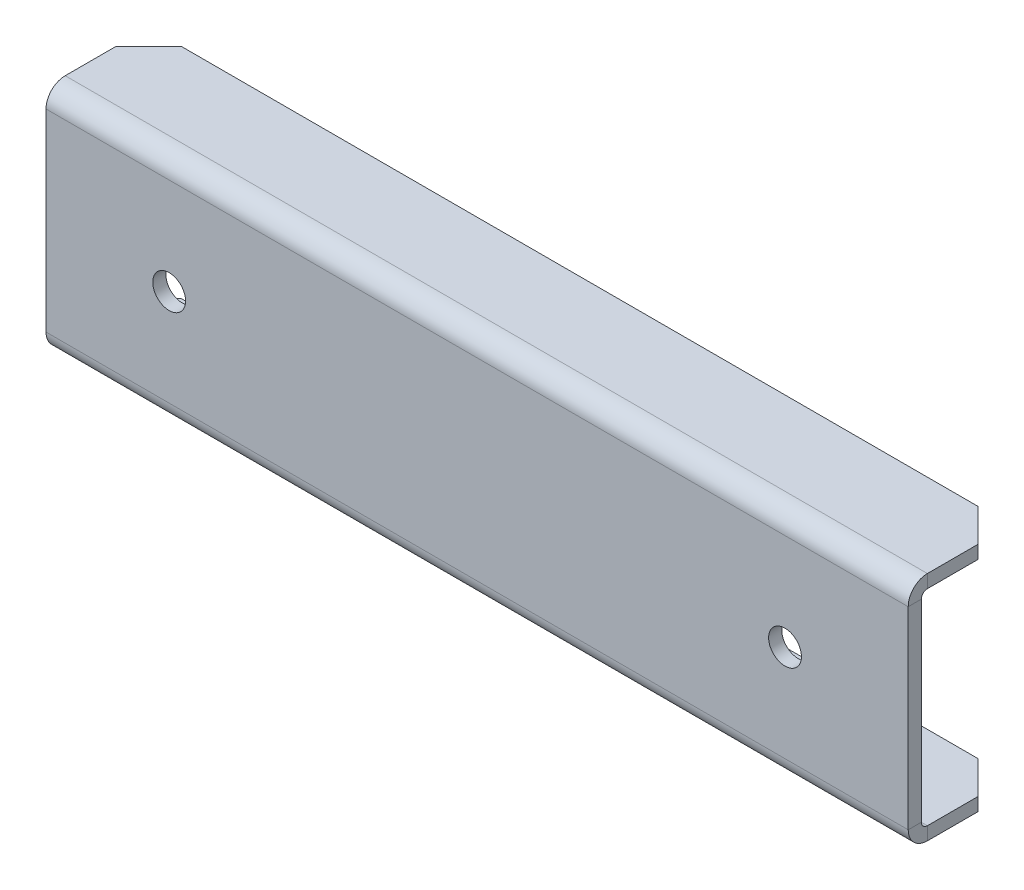
SolidWorks part; units mm, degrees
note: The reader was unsure of these and kept them because the rebuilt part matched: flange length of "边线-法兰1".
ref_plane "前视基准面" through (0, 0, 0) normal (0, 0, 1) x (1, 0, 0)
ref_plane "上视基准面" through (0, 0, 0) normal (0, 1, 0) x (1, 0, 0)
ref_plane "右视基准面" through (0, 0, 0) normal (1, 0, 0) x (0, 0, -1)
sketch "草图1" plane through (0, 0, 0) normal (0, 0, 1) x (1, 0, 0)
  line L0 (-137.2107, 0) -> (176.0178, 0) construction
  line L2 (0, -108.2314) -> (0, 95.1277) construction
  line L3 (-52.5, 12.5) -> (52.5, 12.5)
  line L4 (-52.5, 12.5) -> (-52.5, -12.5)
  line L5 (-52.5, -12.5) -> (52.5, -12.5)
  line L6 (52.5, 12.5) -> (52.5, -12.5)
  dimension "D1" = 105
  dimension "D2" = 25
sheet metal parameters "钣金1" thickness 1.6 parameters "D1"=0.7366
base flange "基体-法兰1" sketch "草图1" thickness 1.6 reverse thickness direction no parameters "D1"=0.7366
edge flange "边线-法兰1" sketch "草图9" flange profiles "草图9", "草图10" flange angle 90 flange length 12.5 flange position material outside bend radius 0.7366 thickness 1.6 relief rectangular parameters "D6"=10, "D8"=1
sketch "草图9" plane through (0, 12.5, -1.6) normal (0, 1, 0) x (1, 0, 0)
  line L0 (52.5, 0) -> (-52.5, 0) construction
  line L1 (52.5, 0) -> (-52.5, 0)
  line L2 (-52.5, 0) -> (-52.5, 10.9)
  line L3 (-52.5, 10.9) -> (52.5, 10.9)
  line L4 (52.5, 10.9) -> (52.5, 0)
sketch "草图10" plane through (0, -12.5, -1.6) normal (0, -1, 0) x (-1, 0, 0)
  line L0 (52.5, 0) -> (-52.5, 0) construction
  line L1 (52.5, 0) -> (-52.5, 0)
  line L2 (-52.5, 0) -> (-52.5, 10.9)
  line L3 (-52.5, 10.9) -> (52.5, 10.9)
  line L4 (52.5, 10.9) -> (52.5, 0)
bend "边线折弯1" bend radius 0.7366 bend angle 90 parameters "D5"=1
bend "边线折弯2" bend radius 0.7366 bend angle 90 parameters "D5"=2
sketch "草图12" plane through (0, 0, 0) normal (0, 1, 0) x (1, 0, 0)
  line L0 (-52.5, 8.5) -> (-48.5, 12.5)
  line L1 (48.5, 12.5) -> (52.5, 12.5)
  line L5 (48.5, 12.5) -> (52.5, 8.5)
  line L6 (-52.5, 8.5) -> (-52.5, 12.5)
  line L7 (-48.5, 12.5) -> (-52.5, 12.5)
  line L9 (52.5, 8.5) -> (52.5, 12.5)
  dimension "D1" = 4
  dimension "D2" = 4
  dimension "D3" = 4
  dimension "D4" = 4
extrude "切除-拉伸1" cut sketch "草图12" against normal through all and the other way through all normal cut yes
sketch "草图13" plane through (0, 0, -1.6) normal (0, 0, -1) x (-1, 0, 0)
  line L0 (137.2107, 0) -> (-176.0178, 0) construction
  line L1 (-52.5, -11.7634) -> (-52.5, 11.7634) construction
  circle A0 centre (-37.5, 0) radius 2
  point P4 (-52.5, 0)
  dimension "D2" = 4
  dimension "D1" = 15
extrude "切除-拉伸2" cut sketch "草图13" against normal through all normal cut yes
mirror "镜向1" about plane through (0, 0, 0) normal (1, 0, 0) of "切除-拉伸2"
flat pattern "平板型式1" [suppressed]
sketch "折弯-线1" plane through (0, 0, 0) normal (0, 1, 0) x (-1, 0, 0)
sketch3d "边界框1" [suppressed]
  line L0 (0, 0, 0) -> (-105, 0, 0) construction
  line L1 (0, 25, 0) -> (-105, 25, 0) construction
  line L2 (0, 0, 0) -> (0, 25, 0) construction
  line L3 (-105, 0, 0) -> (-105, 25, 0) construction
bend of the flat pattern "展开-<边线折弯1>1"
bend of the flat pattern "展开-<边线折弯2>1"
